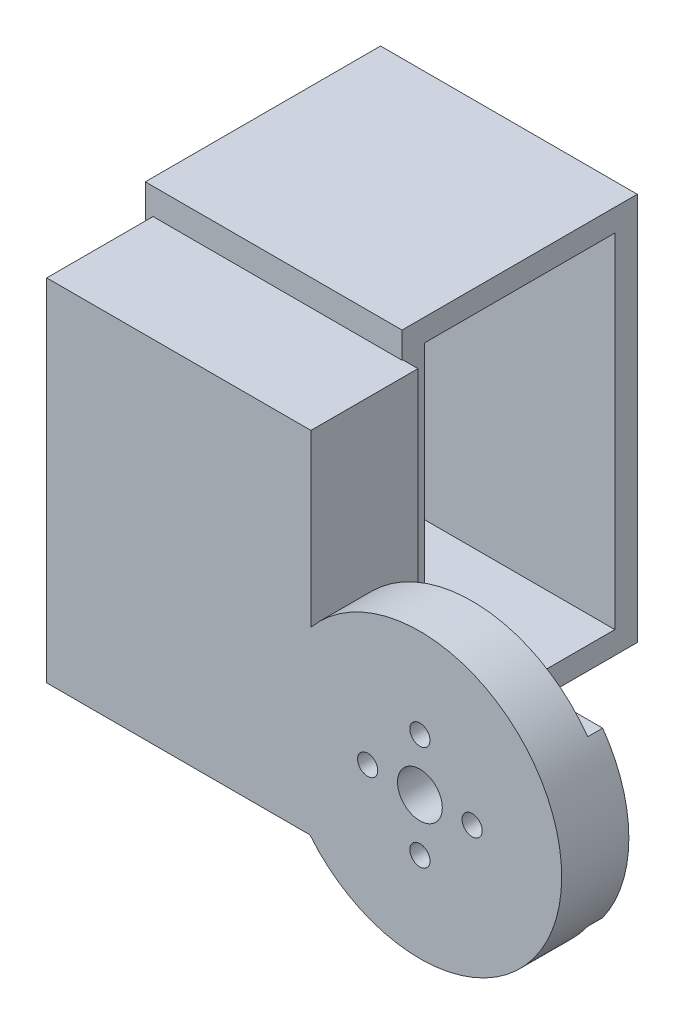
SolidWorks part; units mm, degrees
ref_plane "Front Plane" through (0, 0, 0) normal (0, 0, 1) x (1, 0, 0)
ref_plane "Top Plane" through (0, 0, 0) normal (0, 1, 0) x (1, 0, 0)
ref_plane "Right Plane" through (0, 0, 0) normal (1, 0, 0) x (0, 0, -1)
ref_plane "PZ_p23_000" through (0, 0, 23) normal (0, 0, 1) x (1, 0, 0)
sketch "S_cyl1" plane through (0, 0, 23) normal (0, 0, 1) x (1, 0, 0)
  circle A0 centre (0, 0) radius 19
  dimension "D1_S_cyl1" = 38
extrude "Boss_1" add sketch "S_cyl1" along normal blind 7
ref_plane "PZ_p21_000" through (0, 0, 21) normal (0, 0, 1) x (1, 0, 0)
sketch "S_prism2" plane through (0, 0, 21) normal (0, 0, 1) x (1, 0, 0)
  line L0 (-15.4919, 11) -> (15.4919, 11)
  line L1 (15.4919, -11) -> (-15.4919, -11)
  arc A0 (15.4919, 11) -> (15.4919, -11) centre (0, 0) cw
  arc A1 (-15.4919, -11) -> (-15.4919, 11) centre (0, 0) cw
extrude "Boss_2" add sketch "S_prism2" along normal blind 2.1
ref_plane "PZ_p19_600" through (0, 0, 19.6) normal (0, 0, 1) x (1, 0, 0)
sketch "S_box3" plane through (0, 0, 19.6) normal (0, 0, 1) x (1, 0, 0)
  line L0 (-14.5, -5) -> (14, -5)
  line L1 (14, -5) -> (14, 5)
  line L2 (14, 5) -> (-14.5, 5)
  line L3 (-14.5, 5) -> (-14.5, -5)
  dimension "P1" = 14.5
  dimension "P2" = 5
  dimension "P3" = 14
  dimension "P4" = 5
  dimension "P5" = 14
  dimension "P6" = 5
  dimension "P7" = 14.5
  dimension "P8" = 5
extrude "Boss_3" add sketch "S_box3" along normal blind 1.5
ref_plane "PZ_p15_660" through (0, 0, 15.66) normal (0, 0, 1) x (1, 0, 0)
sketch "S_box4" plane through (0, 0, 15.66) normal (0, 0, 1) x (1, 0, 0)
  line L0 (-50, -12) -> (-14.6, -12)
  line L1 (-14.6, -12) -> (-14.6, 35)
  line L2 (-14.6, 35) -> (-50, 35)
  line L3 (-50, 35) -> (-50, -12)
  dimension "P1" = 50
  dimension "P2" = 12
  dimension "P3" = 14.6
  dimension "P4" = 12
  dimension "P5" = 14.6
  dimension "P6" = 35
  dimension "P7" = 50
  dimension "P8" = 35
extrude "Boss_4" add sketch "S_box4" along normal blind 14.34
ref_plane "PZ_m15_760" through (0, 0, -15.76) normal (0, 0, 1) x (1, 0, 0)
sketch "S_box5" plane through (0, 0, -15.76) normal (0, 0, 1) x (1, 0, 0)
  line L0 (-51.035, 35.51) -> (-16.635, 35.51)
  line L1 (-16.635, 35.51) -> (-16.635, 38.51)
  line L2 (-16.635, 38.51) -> (-51.035, 38.51)
  line L3 (-51.035, 38.51) -> (-51.035, 35.51)
  dimension "P1" = 51.035
  dimension "P2" = 35.51
  dimension "P3" = 16.635
  dimension "P4" = 35.51
  dimension "P5" = 16.635
  dimension "P6" = 38.51
  dimension "P7" = 51.035
  dimension "P8" = 38.51
extrude "Boss_5" add sketch "S_box5" along normal blind 31.52
sketch "S_box6" plane through (0, 0, -15.76) normal (0, 0, 1) x (1, 0, 0)
  line L0 (-51.035, -13.51) -> (-16.635, -13.51)
  line L1 (-16.635, -13.51) -> (-16.635, -10.51)
  line L2 (-16.635, -10.51) -> (-51.035, -10.51)
  line L3 (-51.035, -10.51) -> (-51.035, -13.51)
  dimension "P1" = 51.035
  dimension "P2" = 13.51
  dimension "P3" = 16.635
  dimension "P4" = 13.51
  dimension "P5" = 16.635
  dimension "P6" = 10.51
  dimension "P7" = 51.035
  dimension "P8" = 10.51
extrude "Boss_6" add sketch "S_box6" along normal blind 31.52
sketch "S_box7" plane through (0, 0, -15.76) normal (0, 0, 1) x (1, 0, 0)
  line L0 (-51.035, -13.51) -> (-16.635, -13.51)
  line L1 (-16.635, -13.51) -> (-16.635, 38.51)
  line L2 (-16.635, 38.51) -> (-51.035, 38.51)
  line L3 (-51.035, 38.51) -> (-51.035, -13.51)
  dimension "P1" = 51.035
  dimension "P2" = 13.51
  dimension "P3" = 16.635
  dimension "P4" = 13.51
  dimension "P5" = 16.635
  dimension "P6" = 38.51
  dimension "P7" = 51.035
  dimension "P8" = 38.51
extrude "Boss_7" add sketch "S_box7" along normal blind 3
ref_plane "PZ_p12_760" through (0, 0, 12.76) normal (0, 0, 1) x (1, 0, 0)
sketch "S_box8" plane through (0, 0, 12.76) normal (0, 0, 1) x (1, 0, 0)
  line L0 (-51.035, -13.51) -> (-16.635, -13.51)
  line L1 (-16.635, -13.51) -> (-16.635, 38.51)
  line L2 (-16.635, 38.51) -> (-51.035, 38.51)
  line L3 (-51.035, 38.51) -> (-51.035, -13.51)
  dimension "P1" = 51.035
  dimension "P2" = 13.51
  dimension "P3" = 16.635
  dimension "P4" = 13.51
  dimension "P5" = 16.635
  dimension "P6" = 38.51
  dimension "P7" = 51.035
  dimension "P8" = 38.51
extrude "Boss_8" add sketch "S_box8" along normal blind 3
sketch "S_box9" plane through (0, 0, -15.76) normal (0, 0, 1) x (1, 0, 0)
  line L0 (-51.035, -13.51) -> (-48.635, -13.51)
  line L1 (-48.635, -13.51) -> (-48.635, 38.51)
  line L2 (-48.635, 38.51) -> (-51.035, 38.51)
  line L3 (-51.035, 38.51) -> (-51.035, -13.51)
  dimension "P1" = 51.035
  dimension "P2" = 13.51
  dimension "P3" = 48.635
  dimension "P4" = 13.51
  dimension "P5" = 48.635
  dimension "P6" = 38.51
  dimension "P7" = 51.035
  dimension "P8" = 38.51
extrude "Boss_9" add sketch "S_box9" along normal blind 31.52
ref_plane "PX_m51_135" through (-51.135, 0, 0) normal (1, 0, 0) x (0, 0, -1)
sketch "S_hole10" plane through (-51.135, 0, 0) normal (1, 0, 0) x (0, 0, -1)
  circle A0 centre (0, 0) radius 11
  dimension "D1_S_hole10" = 22
extrude "Hole_10" cut sketch "S_hole10" along normal blind 2.6
sketch "S_hole11" plane through (-51.135, 0, 0) normal (1, 0, 0) x (0, 0, -1)
  circle A0 centre (-10.25, 8.3) radius 1.1
  dimension "D1_S_hole11" = 2.2
  dimension "P2" = 10.25
  dimension "P3" = 8.3
extrude "Hole_11" cut sketch "S_hole11" along normal blind 2.6
sketch "S_hole12" plane through (-51.135, 0, 0) normal (1, 0, 0) x (0, 0, -1)
  circle A0 centre (10.25, 32.75) radius 1.1
  dimension "D1_S_hole12" = 2.2
  dimension "P2" = 10.25
  dimension "P3" = 32.75
extrude "Hole_12" cut sketch "S_hole12" along normal blind 2.6
sketch "S_hole13" plane through (-51.135, 0, 0) normal (1, 0, 0) x (0, 0, -1)
  circle A0 centre (-10.25, 32.75) radius 1.1
  dimension "D1_S_hole13" = 2.2
  dimension "P2" = 10.25
  dimension "P3" = 32.75
extrude "Hole_13" cut sketch "S_hole13" along normal blind 2.6
ref_plane "PZ_p19_500" through (0, 0, 19.5) normal (0, 0, 1) x (1, 0, 0)
sketch "S_hole14" plane through (0, 0, 19.5) normal (0, 0, 1) x (1, 0, 0)
  circle A0 centre (0, 0) radius 3
  dimension "D1_S_hole14" = 6
extrude "Hole_14" cut sketch "S_hole14" along normal blind 10.6
sketch "S_hole15" plane through (0, 0, 19.5) normal (0, 0, 1) x (1, 0, 0)
  circle A0 centre (7, 0) radius 1.35
  dimension "D1_S_hole15" = 2.7
  dimension "P2" = 7
extrude "Hole_15" cut sketch "S_hole15" along normal blind 10.6
sketch "S_hole16" plane through (0, 0, 19.5) normal (0, 0, 1) x (1, 0, 0)
  circle A0 centre (0, -7) radius 1.35
  dimension "D1_S_hole16" = 2.7
  dimension "P2" = 7
extrude "Hole_16" cut sketch "S_hole16" along normal blind 10.6
sketch "S_hole17" plane through (0, 0, 19.5) normal (0, 0, 1) x (1, 0, 0)
  circle A0 centre (-7, 0) radius 1.35
  dimension "D1_S_hole17" = 2.7
  dimension "P2" = 7
extrude "Hole_17" cut sketch "S_hole17" along normal blind 10.6
sketch "S_hole18" plane through (0, 0, 19.5) normal (0, 0, 1) x (1, 0, 0)
  circle A0 centre (0, 7) radius 1.35
  dimension "D1_S_hole18" = 2.7
  dimension "P2" = 7
extrude "Hole_18" cut sketch "S_hole18" along normal blind 10.6
sketch "S_hole19" plane through (0, 0, 19.5) normal (0, 0, 1) x (1, 0, 0)
  circle A0 centre (7, 0) radius 2.3
  dimension "D1_S_hole19" = 4.6
  dimension "P2" = 7
extrude "Hole_19" cut sketch "S_hole19" along normal blind 4.5
sketch "S_hole20" plane through (0, 0, 19.5) normal (0, 0, 1) x (1, 0, 0)
  circle A0 centre (0, -7) radius 2.3
  dimension "D1_S_hole20" = 4.6
  dimension "P2" = 7
extrude "Hole_20" cut sketch "S_hole20" along normal blind 4.5
sketch "S_hole21" plane through (0, 0, 19.5) normal (0, 0, 1) x (1, 0, 0)
  circle A0 centre (-7, 0) radius 2.3
  dimension "D1_S_hole21" = 4.6
  dimension "P2" = 7
extrude "Hole_21" cut sketch "S_hole21" along normal blind 4.5
sketch "S_hole22" plane through (0, 0, 19.5) normal (0, 0, 1) x (1, 0, 0)
  circle A0 centre (0, 7) radius 2.3
  dimension "D1_S_hole22" = 4.6
  dimension "P2" = 7
extrude "Hole_22" cut sketch "S_hole22" along normal blind 4.5
equation "\"plate_t\" = 3"
equation "\"clearance\" = 0.4"
